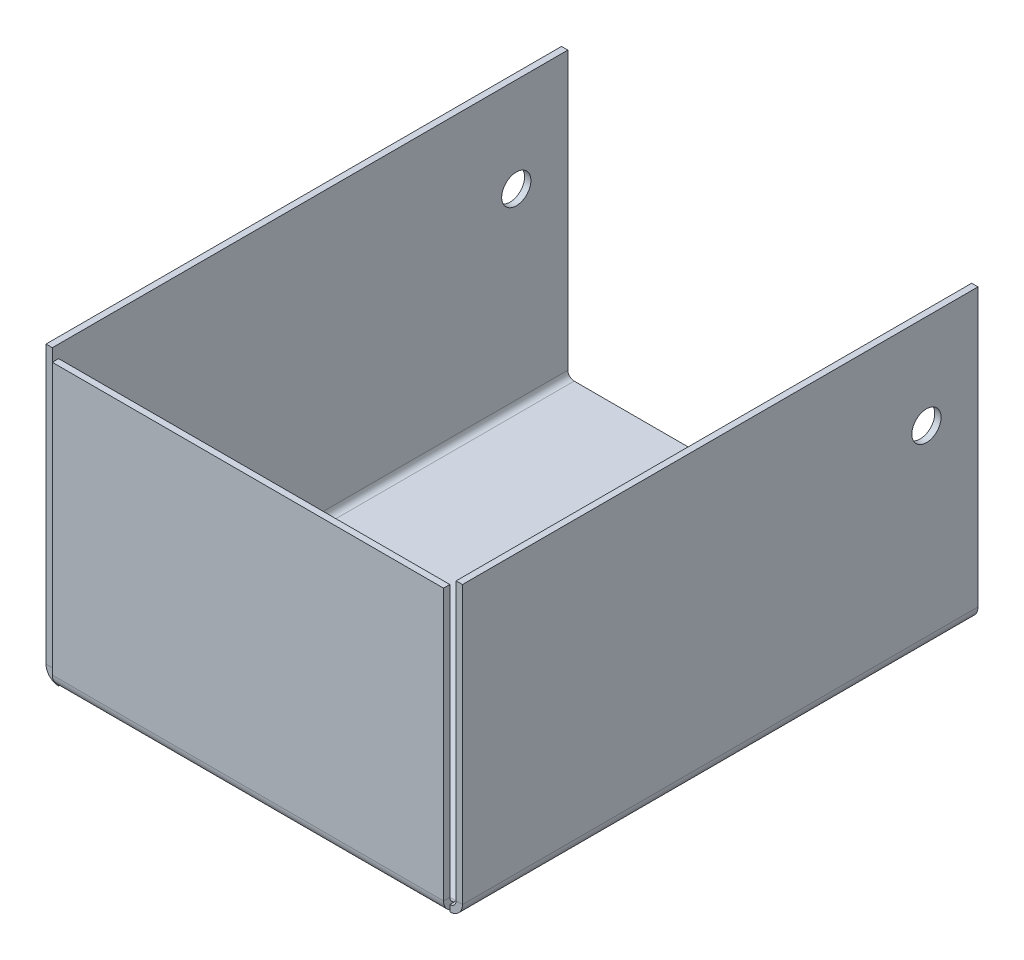
SolidWorks part; units mm, degrees
note: The reader was unsure of these and kept them because the rebuilt part matched: bend radius of "BaseBend1", "BaseBend2"; flange length of "Edge-Flange1".
ref_plane "Front Plane" through (0, 0, 0) normal (0, 0, 1) x (1, 0, 0)
ref_plane "Top Plane" through (0, 0, 0) normal (0, 1, 0) x (1, 0, 0)
ref_plane "Right Plane" through (0, 0, 0) normal (1, 0, 0) x (0, 0, -1)
sketch "Sketch1" plane through (0, 0, 0) normal (0, 0, 1) x (1, 0, 0)
  line L0 (-23.5, 0) -> (23.5, 0)
  line L1 (23.5, 0) -> (23.5, 33)
  line L2 (-23.5, 0) -> (-23.5, 33)
  dimension "D1" = 47
  dimension "D2" = 33
base flange "Base-Flange1" sketch "Sketch1" end condition mid plane depth 60 reverse direction no thickness 0.7366 reverse thickness direction yes bend radius 0.7366
bend "BaseBend1" bend radius 0.7366 bend angle 90 parameters "D5"=1
bend "BaseBend2" bend radius 0.7366 bend angle 90 parameters "D5"=2
edge flange "Edge-Flange1" sketch "Sketch8" flange angle 90 flange length 33 flange position material outside bend radius 0.7366 thickness 0.7366 relief none parameters "D6"=10
sketch "Sketch8" plane through (0, 0, 30) normal (0, 0, 1) x (1, 0, 0)
  line L2 (-22.7634, 0) -> (-22.7634, 32.2634)
  line L3 (-22.7634, 32.2634) -> (22.7634, 32.2634)
  line L4 (22.7634, 32.2634) -> (22.7634, 0)
  line L11 (22.7634, 0) -> (-22.7634, 0) construction
  line L12 (22.7634, 0) -> (-22.7634, 0)
bend "EdgeBend1" bend radius 0.7366 bend angle 90 parameters "D5"=3
sketch "Sketch9" plane through (24.2366, 0, 0) normal (1, 0, 0) x (0, 0, -1)
  line L2 (30, 33) -> (30, 0.7366) construction
  line L3 (-30, 33) -> (30, 33) construction
  point P0 (24, 22)
  point P5 (24, 23.9409)
  dimension "D1" = 6
  dimension "D2" = 11
hole_wizard "M3 Clearance Hole1" positions "Sketch10" profile "Sketch11" hole size "M3" standard "ISO" end condition through all
sketch "Sketch10" plane through (24.2366, 0, 0) normal (1, 0, 0) x (0, 0, -1)
  point P0 (24, 22)
sketch "Sketch11" plane through (24.2366, 22, -24) normal (0, 1, 0) x (0, 0, -1)
  line L0 (0, 0) -> (0, 48.4732)
  line L1 (0, 48.4732) -> (1.7, 48.4732)
  line L2 (1.7, 48.4732) -> (1.7, 0)
  line L5 (1.7, 0) -> (0, 0)
  line L11 (0, -6.35) -> (0, 107.95) construction
  dimension "Thru Hole Dia." = 3.4
  dimension "Thru Hole Depth" = 48.4732
sketch "Sketch13" plane through (0, -0.7366, 0) normal (0, -1, 0) x (1, 0, 0)
  line L1 (22.7634, -30) -> (-22.7634, -30) construction
  circle A0 centre (0, -6.5) radius 3
  point P8 (0, 0)
  dimension "D2" = 6
  dimension "D1" = 23.5
extrude "Cut-Extrude2" cut sketch "Sketch13" against normal through all normal cut yes
sketch "Bend-Lines1" [suppressed] plane through (0, 0, 0) normal (0, 1, 0) x (1, 0, 0)
sketch "Bounding-Box1" [suppressed] plane through (0, 0, 0) normal (0, 1, 0) x (1, 0, 0)
sheet metal parameters "Sheet-Metal1" thickness 0.7366 parameters "D1"=0.7366
flat pattern "Flat-Pattern1" [suppressed]
sketch "Bend-Lines2" plane through (0, 0, 0) normal (0, -1, 0) x (-1, 0, 0)
  line L0 (-22.8946, -30) -> (-22.8946, 30) construction
  line L1 (22.8946, 30) -> (22.8946, -30) construction
  line L2 (-22.8946, -30) -> (-22.8946, 30) construction
  line L3 (22.8946, 30) -> (22.8946, -30) construction
sketch3d "Bounding-Box2" [suppressed]
  line L0 (-78.7892, 60, 0) -> (31.7892, 60, 0) construction
  line L1 (-78.7892, 0, 0) -> (31.7892, 0, 0) construction
  line L2 (-78.7892, 60, 0) -> (-78.7892, 0, 0) construction
  line L3 (31.7892, 60, 0) -> (31.7892, 0, 0) construction
bend of the flat pattern "Flatten-<BaseBend1>1"
bend of the flat pattern "Flatten-<BaseBend2>1"
sheet metal parameters "Sheet-Metal2" thickness 0.7366 parameters "D1"=0.7366
flat pattern "Flat-Pattern1"
sketch "Bend-Lines2" plane through (0, 0, 0) normal (0, -1, 0) x (-1, 0, 0)
  line L0 (-22.8946, -30) -> (-22.8946, 30) construction
  line L1 (22.8946, 30) -> (22.8946, -30) construction
  line L2 (-22.8946, -30) -> (-22.8946, 30) construction
  line L3 (22.8946, 30) -> (22.8946, -30) construction
  line L4 (22.0268, -29.3946) -> (-22.0268, -29.3946) construction
  line L5 (22.0268, -29.3946) -> (-22.0268, -29.3946) construction
sketch3d "Bounding-Box2" [suppressed]
  line L0 (-78.7892, 60, 0) -> (31.7892, 60, 0) construction
  line L1 (-78.7892, -31.7892, 0) -> (31.7892, -31.7892, 0) construction
  line L2 (-78.7892, 60, 0) -> (-78.7892, -31.7892, 0) construction
  line L3 (31.7892, 60, 0) -> (31.7892, -31.7892, 0) construction
bend of the flat pattern "Flatten-<BaseBend1>1"
bend of the flat pattern "Flatten-<BaseBend2>1"
bend of the flat pattern "Flatten-<EdgeBend1>1"
sheet metal parameters "Sheet-Metal3" thickness 0.7366 parameters "D1"=0.7366
flat pattern "Flat-Pattern1" [suppressed]
sketch "Bend-Lines2" plane through (0, -0.7366, 0) normal (0, -1, 0) x (-1, 0, 0)
  line L0 (-23.6312, -30) -> (-23.6312, 30) construction
  line L1 (23.6312, 30) -> (23.6312, -30) construction
  line L2 (-23.6312, -30) -> (-23.6312, 30) construction
  line L3 (23.6312, 30) -> (23.6312, -30) construction
  line L4 (22.7634, -30.1312) -> (-22.7634, -30.1312) construction
  line L5 (22.7634, -30.1312) -> (-22.7634, -30.1312) construction
sketch3d "Bounding-Box2" [suppressed]
  line L0 (-80.2624, 60, 0) -> (33.2624, 60, 0) construction
  line L1 (-80.2624, -32.5258, 0) -> (33.2624, -32.5258, 0) construction
  line L2 (-80.2624, 60, 0) -> (-80.2624, -32.5258, 0) construction
  line L3 (33.2624, 60, 0) -> (33.2624, -32.5258, 0) construction
bend of the flat pattern "Flatten-<BaseBend1>1"
bend of the flat pattern "Flatten-<BaseBend2>1"
bend of the flat pattern "Flatten-<EdgeBend1>1"
sketch "Sketch9-1" [suppressed] plane through (23.7624, -0.7366, 0) normal (0, -1, 0) x (0, 0, -1)
  line L2 (30, 33) -> (30, -80.5247) construction
  line L3 (-30, 33) -> (30, 33) construction
  point P0 (24, 22)
  dimension "D1" = 6
  dimension "D2" = 11
sheet metal parameters "Sheet-Metal5" thickness 0.7366 parameters "D1"=0.7366
flat pattern "Flat-Pattern1" [suppressed]
sketch "Bend-Lines2" plane through (0, -0.7366, 0) normal (0, -1, 0) x (-1, 0, 0)
  line L0 (-23.6312, -30) -> (-23.6312, 30) construction
  line L1 (23.6312, 30) -> (23.6312, -30) construction
  line L2 (-23.6312, -30) -> (-23.6312, 30) construction
  line L3 (23.6312, 30) -> (23.6312, -30) construction
  line L4 (22.7634, -30.1312) -> (-22.7634, -30.1312) construction
  line L5 (22.7634, -30.1312) -> (-22.7634, -30.1312) construction
sketch3d "Bounding-Box2" [suppressed]
  line L0 (-80.2624, 60, 0) -> (33.2624, 60, 0) construction
  line L1 (-80.2624, -32.5258, 0) -> (33.2624, -32.5258, 0) construction
  line L2 (-80.2624, 60, 0) -> (-80.2624, -32.5258, 0) construction
  line L3 (33.2624, 60, 0) -> (33.2624, -32.5258, 0) construction
bend of the flat pattern "Flatten-<BaseBend1>1"
bend of the flat pattern "Flatten-<BaseBend2>1"
bend of the flat pattern "Flatten-<EdgeBend1>1"
sketch "Sketch9-1" [suppressed] plane through (23.7624, -0.7366, 0) normal (0, -1, 0) x (0, 0, -1)
  line L2 (30, 33) -> (30, -80.5247) construction
  line L3 (-30, 33) -> (30, 33) construction
  point P0 (24, 22)
  dimension "D1" = 6
  dimension "D2" = 11
